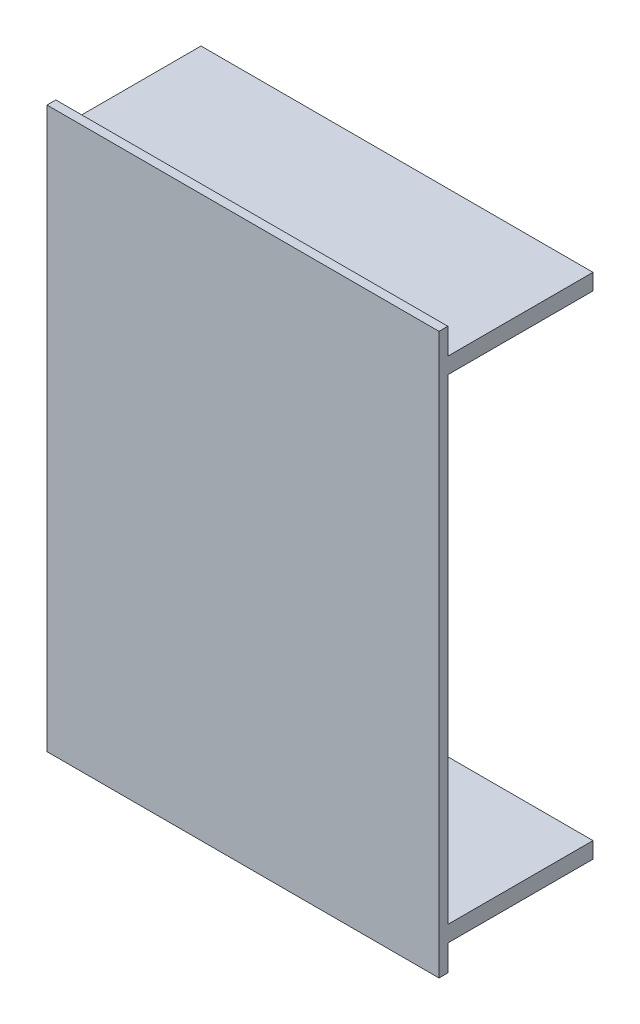
SolidWorks part; units mm, degrees
ref_plane "Front Plane" through (0, 0, 0) normal (0, 0, 1) x (1, 0, 0)
ref_plane "Top Plane" through (0, 0, 0) normal (0, 1, 0) x (1, 0, 0)
ref_plane "Right Plane" through (0, 0, 0) normal (1, 0, 0) x (0, 0, -1)
sketch "Sketch1" plane through (0, 0, 0) normal (0, 0, 1) x (1, 0, 0)
  line L1 (0, 0) -> (280, 0)
  line L2 (0, 0) -> (0, 400)
  line L3 (0, 400) -> (280, 400)
  line L4 (280, 0) -> (280, 400)
  dimension "D1" = 280
  dimension "D2" = 400
extrude "Boss-Extrude1" add sketch "Sketch1" along normal blind 6.3
sketch "Sketch4" plane through (0, 0, 0) normal (1, 0, 0) x (0, 0, -1)
  line L0 (0, 0) -> (0, 400) construction
  line L1 (0, 18.5) -> (103.7, 18.5)
  line L2 (0, 18.5) -> (0, 30)
  line L3 (0, 30) -> (103.7, 30)
  line L4 (103.7, 18.5) -> (103.7, 30)
  line L5 (-6.3, 200) -> (0, 200) construction
  line L6 (-6.3, 0) -> (-6.3, 400) construction
  line L7 (0, 370) -> (103.7, 370)
  line L8 (103.7, 381.5) -> (103.7, 370)
  line L9 (0, 381.5) -> (103.7, 381.5)
  line L10 (0, 381.5) -> (0, 370)
  dimension "D1" = 11.5
  dimension "D2" = 110
  dimension "D3" = 340
extrude "Boss-Extrude2" add sketch "Sketch4" along normal up to surface (280 mm away) up to face at (280, 200, 3.15)
ref_plane "Plane1" through (0, 0, -103.7) normal (0, 0, -1) x (-1, 0, 0)
ref_plane "Plane2" through (0, 200, 0) normal (0, 1, 0) x (1, 0, 0)
ref_plane "Plane3" through (140, 0, 0) normal (1, 0, 0) x (0, 0, -1)
ref_plane "Plane4" through (0, 0, 3.15) normal (0, 0, -1) x (-1, 0, 0)
sketch "Sketch5" plane through (0, 0, 3.15) normal (0, 0, -1) x (-1, 0, 0)
  line L0 (-140, 60.5) -> (-140, -60.5) construction
  line L1 (57.035, 200) -> (-57.035, 200) construction
  line L3 (-280, 0) -> (0, 0)
  line L4 (-280, 0) -> (-280, 400)
  line L5 (-280, 400) -> (0, 400)
  line L6 (0, 0) -> (0, 400)
  line L7 (-280, 0) -> (0, 400) construction
  line L8 (-280, 400) -> (0, 0) construction
  point P0 (-140, 200)
  point P1 (0, 0)
  point P8 (-140, 200)
